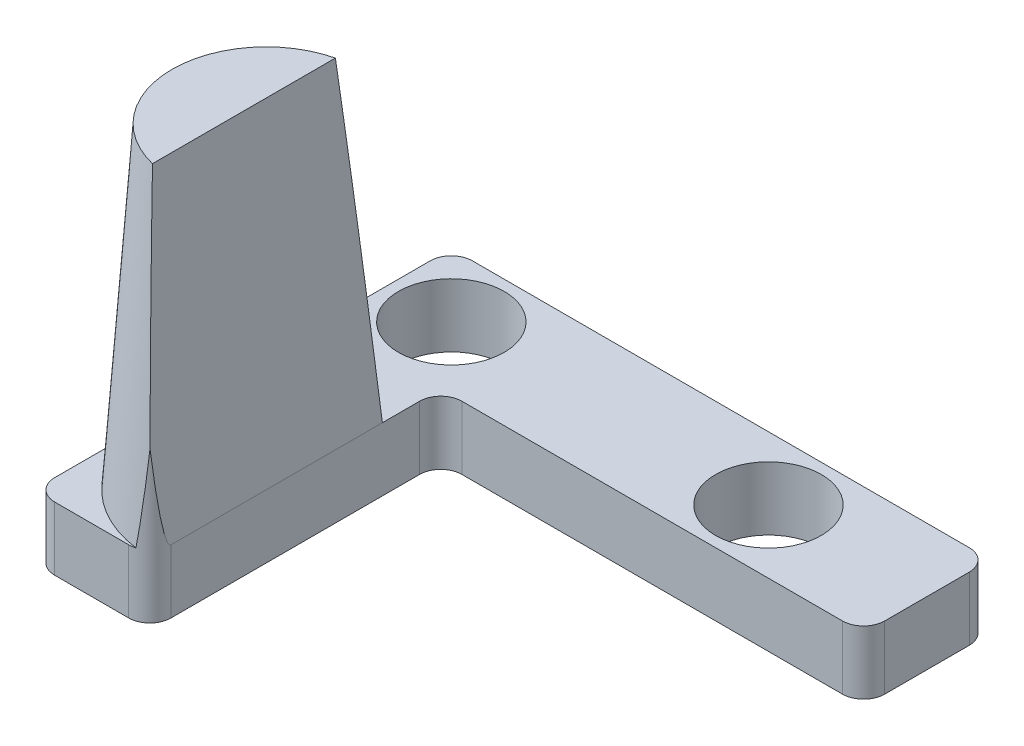
SolidWorks part; units mm, degrees
ref_plane "Front Plane" through (0, 0, 0) normal (0, 0, 1) x (1, 0, 0)
ref_plane "Top Plane" through (0, 0, 0) normal (0, 1, 0) x (1, 0, 0)
ref_plane "Right Plane" through (0, 0, 0) normal (1, 0, 0) x (0, 0, -1)
sketch "Sketch1" plane through (0, 0, 0) normal (0, 1, 0) x (1, 0, 0)
  line L0 (-7.5, 0) -> (-7.5, -3) construction
  line L1 (0, 0) -> (-25.5, 0)
  line L2 (0, 0) -> (0, -6)
  line L3 (0, -6) -> (-20, -6)
  line L6 (-20, -6) -> (-20, -19.76)
  line L7 (-20, -19.76) -> (-25.5, -19.76)
  line L8 (-25.5, 0) -> (-25.5, -19.76)
  line L9 (-7.5, -3) -> (-7.5, -6) construction
  line L10 (-7.5, -6) -> (-7.5, -3) construction
  line L11 (0, -3) -> (-7.5, -3) construction
  circle A0 centre (-7.5, -3) radius 2.5
  circle A1 centre (-22.5, -3) radius 2.5
  dimension "D2" = 5
  dimension "D1" = 15
  dimension "D3" = 3
  dimension "D4" = 3
  dimension "D5" = 13.76
  dimension "D6" = 5.5
  dimension "D7" = 20
extrude "Boss-Extrude1" add sketch "Sketch1" along normal blind 3 contours L7 L8 L1 L2 L3 L6 | A1 | A0
sketch "Sketch3" plane through (0, 3, 0) normal (0, 1, 0) x (1, 0, 0)
  line L1 (-25.5, 0) -> (-25.5, -19.76) construction
  line L2 (-20, -8.76) -> (-20, -19.76)
  line L3 (-20, -6) -> (-20, -19.76) construction
  line L4 (-20, -19.76) -> (-25.5, -19.76) construction
  arc A1 (-20, -8.76) -> (-20, -19.76) centre (-20, -14.26) ccw
extrude "Boss-Extrude2" add sketch "Sketch3" along normal blind 15 draft 4
fillet "Fillet2" radius 1 1 edges at (-20, 1.5, 6)
fillet "Fillet3" radius 1 1 edges at (-20, 1.5, 19.76)
fillet "Fillet4" radius 1 1 edges at (-25.5, 1.5, 19.76)
fillet "Fillet5" radius 1 1 edges at (-25.5, 1.5, 0)
fillet "Fillet6" radius 1 1 edges at (0, 1.5, 0)
fillet "Fillet7" radius 1 1 edges at (0, 1.5, 6)
